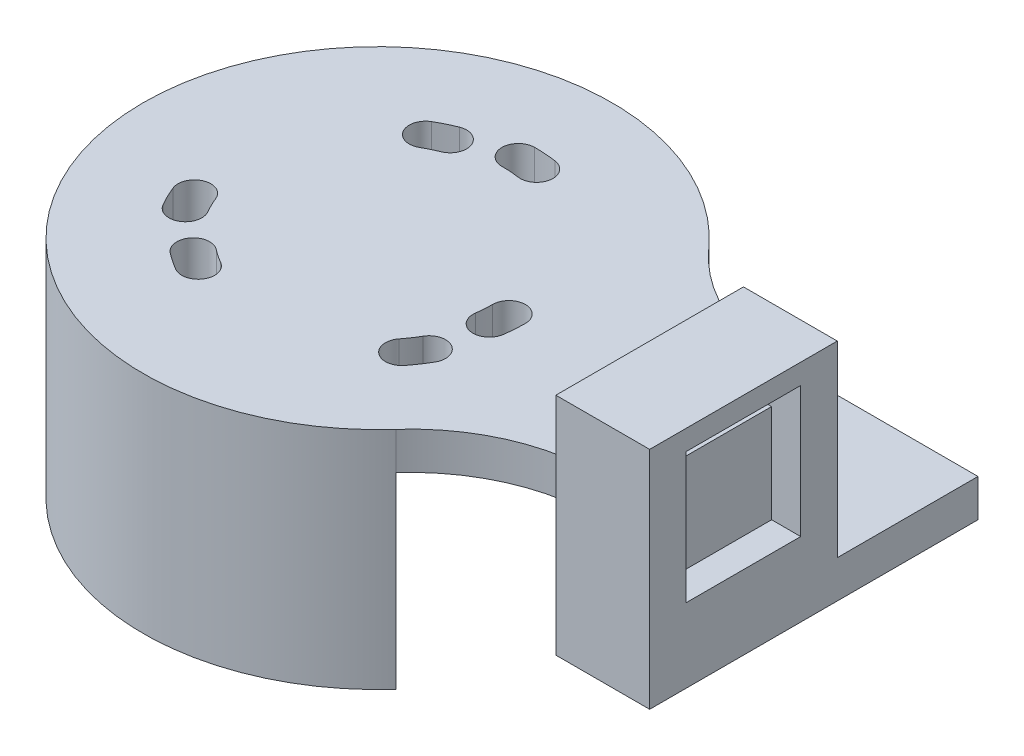
SolidWorks part; units mm, degrees
ref_plane "Front Plane" through (0, 0, 0) normal (0, 0, 1) x (1, 0, 0)
ref_plane "Top Plane" through (0, 0, 0) normal (0, 1, 0) x (1, 0, 0)
ref_plane "Right Plane" through (0, 0, 0) normal (1, 0, 0) x (0, 0, -1)
sketch "Sketch3" plane through (0, 0, 0) normal (0, 1, 0) x (1, 0, 0)
  line L0 (22.9129, 10) -> (44, 10)
  line L5 (54, 10) -> (54, -25)
  line L8 (44, -10) -> (22.9129, -10)
  line L10 (0, 0) -> (38.9129, 0) construction
  line L12 (44, 10) -> (44, -10) construction
  line L13 (44, -10) -> (44, -25)
  line L14 (44, -25) -> (54, -25)
  line L15 (44, 10) -> (54, 10)
  arc A5 (22.9129, 10) -> (22.9129, -10) centre (0, 0) ccw
  point P0 (0, 0)
  point P4 (44, 0)
  dimension "D1" = 50
  dimension "D2" = 54
  dimension "D3" = 10
  dimension "D4" = 15
  dimension "D5" = 20
extrude "Boss-Extrude1" add sketch "Sketch3" along normal blind 4
fillet "Fillet1" radius 20 2 edges at (22.9129, 2, 10) (22.9129, 2, -10)
sketch "Sketch1" plane through (103.3827, 0, 0) normal (0, 1, 0) x (1, 0, 0)
  line L2 (-103.3827, -42.2854) -> (-103.3827, 42.2854) construction
  line L16 (-21.097, 0) -> (-103.3827, 0) construction
  circle A9 centre (-76.4698, 0) radius 2.25 construction
  circle A16 centre (-50.4698, 0) radius 2.25 construction
  circle A19 centre (-66.4698, 0) radius 2.75
  arc A20 (-91.9079, -6.625) -> (-92.9415, -8.1575) centre (-103.3827, 0) cw
  arc A21 (-88.8768, -8.375) -> (-90.1835, -10.3123) centre (-103.3827, 0) cw
  arc A22 (-92.9415, -8.1575) -> (-90.1835, -10.3123) centre (-91.5625, -9.2349) ccw
  arc A23 (-91.9079, -6.625) -> (-88.8768, -8.375) centre (-90.3923, -7.5) cw
  arc A24 (-91.1327, 0) -> (-91.2519, -1.7049) centre (-103.3827, 0) cw
  arc A25 (-87.6327, 0) -> (-87.786, -2.192) centre (-103.3827, 0) cw
  arc A26 (-91.2519, -1.7049) -> (-87.786, -2.192) centre (-89.5189, -1.9484) ccw
  arc A27 (-87.6327, 0) -> (-91.1327, 0) centre (-89.3827, 0) ccw
  arc A28 (-114.8575, -6.625) -> (-117.8886, -8.375) centre (-116.3731, -7.5) cw
  arc A29 (-117.8886, -8.375) -> (-118.913, -6.2747) centre (-103.3827, 0) cw
  arc A30 (-115.6679, -4.9635) -> (-118.913, -6.2747) centre (-117.2904, -5.6191) ccw
  arc A31 (-114.8575, -6.625) -> (-115.6679, -4.9635) centre (-103.3827, 0) cw
  arc A32 (-111.2577, -13.6399) -> (-109.5077, -10.6088) centre (-110.3827, -12.1244) ccw
  arc A33 (-109.5077, -10.6088) -> (-110.9245, -9.6531) centre (-103.3827, 0) cw
  arc A34 (-110.9245, -9.6531) -> (-113.0794, -12.4112) centre (-112.002, -11.0322) ccw
  arc A35 (-111.2577, -13.6399) -> (-113.0794, -12.4112) centre (-103.3827, 0) cw
  arc A36 (-103.3827, 13.25) -> (-103.3827, 16.75) centre (-103.3827, 15) cw
  arc A37 (-103.3827, 16.75) -> (-101.0515, 16.587) centre (-103.3827, 0) cw
  arc A38 (-101.5386, 13.1211) -> (-101.0515, 16.587) centre (-101.2951, 14.854) ccw
  arc A39 (-103.3827, 13.25) -> (-101.5386, 13.1211) centre (-103.3827, 0) cw
  arc A40 (-111.2577, 13.6399) -> (-109.5077, 10.6088) centre (-110.3827, 12.1244) ccw
  arc A41 (-109.5077, 10.6088) -> (-107.9716, 11.358) centre (-103.3827, 0) cw
  arc A42 (-107.9716, 11.358) -> (-109.2827, 14.6031) centre (-108.6272, 12.9806) ccw
  arc A43 (-111.2577, 13.6399) -> (-109.2827, 14.6031) centre (-103.3827, 0) cw
  point P44 (-103.3827, 0)
  dimension "D4" = 15
  dimension "D3" = 8
  dimension "D2" = 4.5
  dimension "D1" = 26.9129
  dimension "D5" = 5.5
  dimension "D8" = 1.75
  dimension "D11" = 1.75
  dimension "D6" = 10
  dimension "D7" = 26
  dimension "D9" = 14
  dimension "D10" = 8
  dimension "D12" = 22
  dimension "D13" = 3
extrude "Cut-Extrude3" cut sketch "Sketch1" along normal through all
sketch "Sketch5" plane through (0, 0, 0) normal (0, -1, 0) x (-1, 0, 0)
  line L1 (-23.9129, -10) -> (-71.2761, -10)
  line L2 (-23.9129, -10) -> (-23.9129, 10)
  line L3 (-23.9129, 10) -> (-71.2761, 10)
  line L4 (-71.2761, -10) -> (-71.2761, 10)
  point P4 (-23.9129, 0)
  dimension "D1" = 20
  dimension "D2" = 3
sketch "Sketch4" plane through (0, 0, 0) normal (0, -1, 0) x (1, 0, 0)
  line L0 (18.6339, 16.6667) -> (17.4523, 15.6098)
  line L1 (17.4523, -15.6098) -> (18.6339, -16.6667)
  arc A0 (18.6339, 16.6667) -> (18.6339, -16.6667) centre (0, 0) ccw
  arc A1 (18.6339, 16.6667) -> (18.6339, -16.6667) centre (0, 0) ccw construction
  arc A2 (14.7472, 15.6452) -> (14.7472, -15.6452) centre (0, 0) ccw
  arc A3 (14.7472, 15.6452) -> (17.4523, 15.6098) centre (16.119, 17.1005) ccw
  arc A4 (14.7472, -15.6452) -> (17.4523, -15.6098) centre (16.119, -17.1005) cw
  dimension "D3" = 3.5
  dimension "D4" = 2
extrude "Boss-Extrude2" add sketch "Sketch4" along normal blind 20 contours A2 A4 L1 A0 L0 A3
sketch "Sketch7" plane through (0, 4, 0) normal (0, 1, 0) x (1, 0, 0)
  line L0 (54, -25) -> (54, 10) construction
  line L1 (44, -5) -> (54, -5)
  line L2 (44, -5) -> (44, -25)
  line L3 (44, -25) -> (54, -25)
  line L4 (54, -5) -> (54, -25)
  line L6 (44, -25) -> (54, -25) construction
  dimension "D1" = 10
  dimension "D2" = 20
extrude "Boss-Extrude3" add sketch "Sketch7" along normal blind 20 contours L4 L3 L2 L1
sketch "Sketch8" plane through (54, 0, 0) normal (1, 0, 0) x (0, 0, -1)
  line L0 (-5, 24) -> (-5, 4) construction
  line L1 (-21.1, 20.1) -> (-8.9, 20.1)
  line L2 (-21.1, 20.1) -> (-21.1, 7.9)
  line L3 (-21.1, 7.9) -> (-8.9, 7.9)
  line L4 (-8.9, 20.1) -> (-8.9, 7.9)
  line L5 (-8.9, 20.1) -> (-21.1, 7.9) construction
  line L6 (-5, 24) -> (-25, 24) construction
  line L8 (-21.1, 21.85) -> (-8.9, 21.85)
  line L9 (-21.1, 21.85) -> (-21.1, 18.35)
  line L10 (-21.1, 18.35) -> (-8.9, 18.35)
  line L11 (-8.9, 21.85) -> (-8.9, 18.35)
  line L12 (-21.1, 21.85) -> (-8.9, 18.35) construction
  line L13 (-21.1, 18.35) -> (-8.9, 21.85) construction
  point P7 (-15, 24)
  point P10 (-5, 14)
  point P11 (-15, 20.1)
  point P16 (-15, 14)
  dimension "D1" = 12.2
  dimension "D2" = 3.5
extrude "Cut-Extrude4" cut sketch "Sketch8" against normal blind 3.1 contours L2 L3 L4 L1
extrude "Cut-Extrude5" cut sketch "Sketch8<3>" against normal up to next contours L8 L11 L10 L9
sketch "Sketch8<3>" plane through (54, 0, 0) normal (1, 0, 0) x (0, 0, -1) same geometry as "Sketch8"
